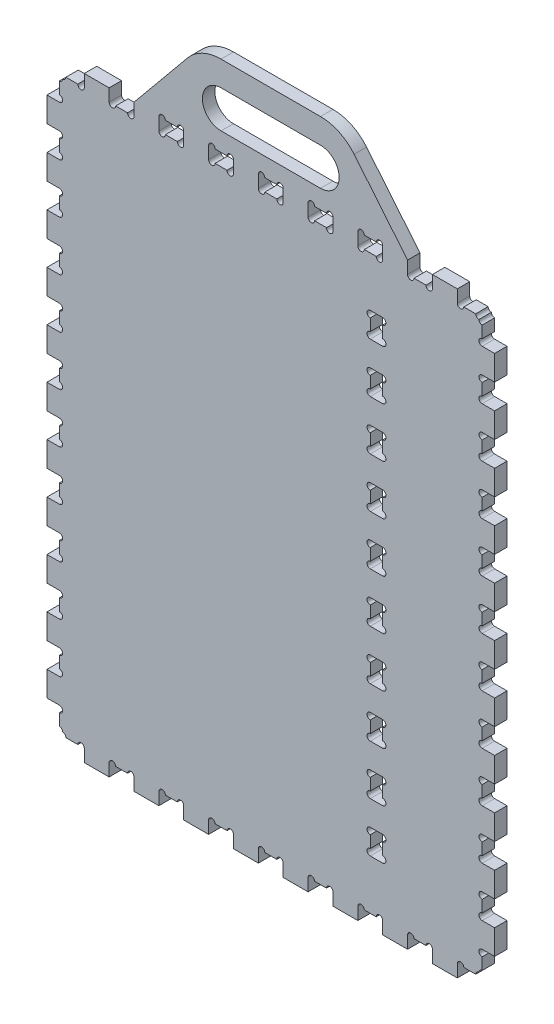
SolidWorks part; units mm, degrees
ref_plane "Front Plane" through (0, 0, 0) normal (0, 0, 1) x (1, 0, 0)
ref_plane "Top Plane" through (0, 0, 0) normal (0, 1, 0) x (1, 0, 0)
ref_plane "Right Plane" through (0, 0, 0) normal (1, 0, 0) x (0, 0, -1)
sketch "Sketch1" plane through (0, 0, 0) normal (0, 0, 1) x (1, 0, 0)
  line L1 (228.6, -304.8) -> (-228.6, -304.8)
  line L2 (228.6, -304.8) -> (228.6, 304.8)
  line L3 (228.6, 304.8) -> (-228.6, 304.8)
  line L4 (-228.6, -304.8) -> (-228.6, 304.8)
  line L5 (228.6, -304.8) -> (-228.6, 304.8) construction
  line L6 (228.6, 304.8) -> (-228.6, -304.8) construction
  line L9 (-203.2, 304.8) -> (-228.6, 304.8) construction
  point P0 (0, 0)
  dimension "D1" = 457.2
  dimension "D2" = 609.6
extrude "Boss-Extrude1" add sketch "Sketch1" along normal blind 12.7
sketch "Sketch2" plane through (0, 0, 12.7) normal (0, 0, 1) x (1, 0, 0)
  line L0 (228.6, 304.8) -> (-228.6, 304.8) construction
  line L1 (-215.9, 292.1) -> (-228.6, 292.1) construction
  line L2 (-215.9, 304.8) -> (-190.5, 304.8)
  line L3 (-215.9, 304.8) -> (-215.9, 292.1)
  line L4 (-215.9, 292.1) -> (-190.5, 292.1)
  line L5 (-190.5, 304.8) -> (-190.5, 292.1)
  line L6 (-228.6, 304.8) -> (-228.6, -304.8) construction
  circle A0 centre (-212.598, 292.1) radius 3.302
  circle A1 centre (-193.802, 292.1) radius 3.302
  line M10 (228.6, 304.8) -> (-228.6, 304.8)
  dimension "D4" = 6.604
  dimension "D5" = 6.604
  dimension "D1" = 25.4
  dimension "D2" = 12.7
  dimension "D3" = 12.7
extrude "Cut-Extrude1" cut sketch "Sketch2" against normal through all contours A1 L5 L3 A0 L4 M10 | L4 A0 | L4 A0 | L4 A1 | L4 A1 region at (-203.2, 299.0379, 12.7) region at (-212.598, 293.5014, 12.7) region at (-212.598, 290.6986, 12.7) region at (-193.802, 290.6986, 12.7) region at (-193.802, 293.5014, 12.7)
pattern_linear "LPattern1" count 9 spacing 50.8 along (1, 0, 0) of "Cut-Extrude1"
sketch "Sketch6" plane through (0, 0, 12.7) normal (0, 0, 1) x (1, 0, 0)
  line L1 (-228.6, 304.8) -> (-215.9, 304.8)
  line L2 (-228.6, 304.8) -> (-228.6, 292.1)
  line L3 (-228.6, 292.1) -> (-215.9, 292.1)
  line L4 (-215.9, 304.8) -> (-215.9, 292.1)
extrude "Cut-Extrude4" cut sketch "Sketch6" against normal through all
sketch "Sketch3" plane through (0, 0, 12.7) normal (0, 0, 1) x (1, 0, 0)
  line L0 (-228.6, 292.1) -> (-228.6, -304.8) construction
  line L1 (-228.6, 292.1) -> (-215.9, 292.1)
  line L2 (-228.6, 292.1) -> (-228.6, 266.7)
  line L3 (-228.6, 266.7) -> (-215.9, 266.7)
  line L4 (-215.9, 292.1) -> (-215.9, 266.7)
  line L5 (-215.9, 292.1) -> (-182.9158, 292.1) construction
  line L6 (-182.9158, 292.1) -> (-182.9158, 304.8) construction
  line L8 (-165.1, 304.8) -> (-190.5, 304.8) construction
  circle A0 centre (-215.9, 288.798) radius 3.302
  circle A1 centre (-215.9, 270.002) radius 3.302
  dimension "D3" = 6.604
  dimension "D4" = 6.604
  dimension "D1" = 25.4
  dimension "D2" = 12.7
  dimension "D5" = 12.7
extrude "Cut-Extrude2" cut sketch "Sketch3" against normal through all contours A1 L4 A0 L1 L2 L3 | L4 A0 | L4 A0 | L4 A1 | L4 A1 region at (-222.8379, 279.4, 12.7) region at (-214.4986, 288.798, 12.7) region at (-217.3014, 288.798, 12.7) region at (-217.3014, 270.002, 12.7) region at (-214.4986, 270.002, 12.7)
pattern_linear "LPattern2" count 12 spacing 50.8 along (0, -1, 0) of "Cut-Extrude2"
ref_plane "Plane1" through (0, 0, 0) normal (1, 0, 0) x (0, 0, -1)
ref_plane "Plane2" through (0, 0, 0) normal (0, 1, 0) x (1, 0, 0)
mirror "Mirror6" about plane through (0, 0, 0) normal (1, 0, 0) of "Cut-Extrude4"
mirror "Mirror7" about plane through (0, 0, 0) normal (0, 1, 0) of "Mirror6", "Cut-Extrude4"
mirror "Mirror1" about plane through (0, 0, 0) normal (1, 0, 0) of "LPattern2"
mirror "Mirror2" about plane through (0, 0, 0) normal (0, 1, 0) of "LPattern1"
sketch "Sketch9" plane through (0, 0, 0) normal (0, 0, -1) x (-1, 0, 0)
  line L0 (-139.7, 304.8) -> (139.7, 304.8)
  line L1 (-139.7, 304.8) -> (-114.3, 304.8) construction
  line L2 (114.3, 304.8) -> (139.7, 304.8) construction
  line L3 (139.7, 304.8) -> (139.7, 292.1) construction
  line L4 (139.7, 304.8) -> (85.1274, 371.1389)
  line L5 (50.8, 387.35) -> (-50.8, 387.35)
  line L6 (-85.1274, 371.1389) -> (-139.7, 304.8)
  line L7 (-50.8, 342.9) -> (50.8, 342.9) construction
  line L8 (-50.8, 361.95) -> (50.8, 361.95)
  line L9 (-50.8, 323.85) -> (50.8, 323.85)
  line L10 (23.5425, 342.9) -> (23.5425, 304.8) construction
  line L12 (0, 292.1) -> (0, 342.9) construction
  line L13 (6.096, 292.1) -> (-6.096, 292.1) construction
  arc A0 (-50.8, 361.95) -> (-50.8, 323.85) centre (-50.8, 342.9) ccw
  arc A1 (50.8, 323.85) -> (50.8, 361.95) centre (50.8, 342.9) ccw
  arc A2 (-50.8, 387.35) -> (-85.1274, 371.1389) centre (-50.8, 342.9) ccw
  arc A4 (85.1274, 371.1389) -> (50.8, 387.35) centre (50.8, 342.9) ccw
  arc A5 (23.5425, 307.7883) -> (27.9047, 304.8) centre (50.8, 342.9) ccw
  point P12 (0, 342.9)
  dimension "D4" = 19.05
  dimension "D1" = 101.6
  dimension "D3" = 38.1
extrude "Boss-Extrude3" add sketch "Sketch9" against normal blind 12.7 contours L4 A4 L5 A2 L6 L0 A1 L9 A0 L8 region at (110.1638, 336.1186, 0)
sketch "Sketch10" plane through (0, 0, 0) normal (0, 0, -1) x (-1, 0, 0)
  line L0 (-114.3, 304.8) -> (-88.9, 304.8) construction
  circle A0 centre (-110.998, 304.8) radius 3.302
  circle A1 centre (-92.202, 304.8) radius 3.302
  arc A2 (-114.3, 292.1) -> (-107.696, 292.1) centre (-110.998, 292.1) ccw construction
  arc A3 (-95.504, 292.1) -> (-88.9, 292.1) centre (-92.202, 292.1) ccw construction
extrude "Cut-Extrude6" cut sketch "Sketch10" against normal blind 12.7
pattern_linear "LPattern3" count 5 spacing 50.8 along (-1, 0, 0) of "Cut-Extrude6"
sketch "Sketch11" plane through (0, 0, 0) normal (0, 0, -1) x (-1, 0, 0)
  line L0 (-114.3, 241.3) -> (-215.9, 241.3) construction
  line L1 (-114.3, 241.3) -> (-101.6, 241.3)
  line L2 (-114.3, 241.3) -> (-114.3, 215.9)
  line L3 (-114.3, 215.9) -> (-101.6, 215.9)
  line L4 (-101.6, 241.3) -> (-101.6, 215.9)
  circle A0 centre (-114.3, 237.998) radius 3.302
  circle A1 centre (-114.3, 219.202) radius 3.302
  circle A2 centre (-101.6, 219.202) radius 3.302
  circle A3 centre (-101.6, 237.998) radius 3.302
  dimension "D3" = 6.604
  dimension "D1" = 12.7
  dimension "D2" = 25.4
  dimension "D4" = 101.6
extrude "Cut-Extrude7" cut sketch "Sketch11" against normal through all contours A3 L1 A0 L2 A1 L3 A2 L4 | L2 A0 | L2 A1 | L4 A2 | L4 A2 | L2 A0 | L2 L3 L4 L1 | A3 region at (112.8986, 237.998, 0) region at (107.95, 228.6, 0) region at (115.7014, 237.998, 0) region at (115.7014, 219.202, 0) region at (100.1986, 219.202, 0) region at (103.0014, 219.202, 0)
pattern_linear "LPattern4" count 10 spacing 50.8 along (0, -1, 0) of "Cut-Extrude7"
